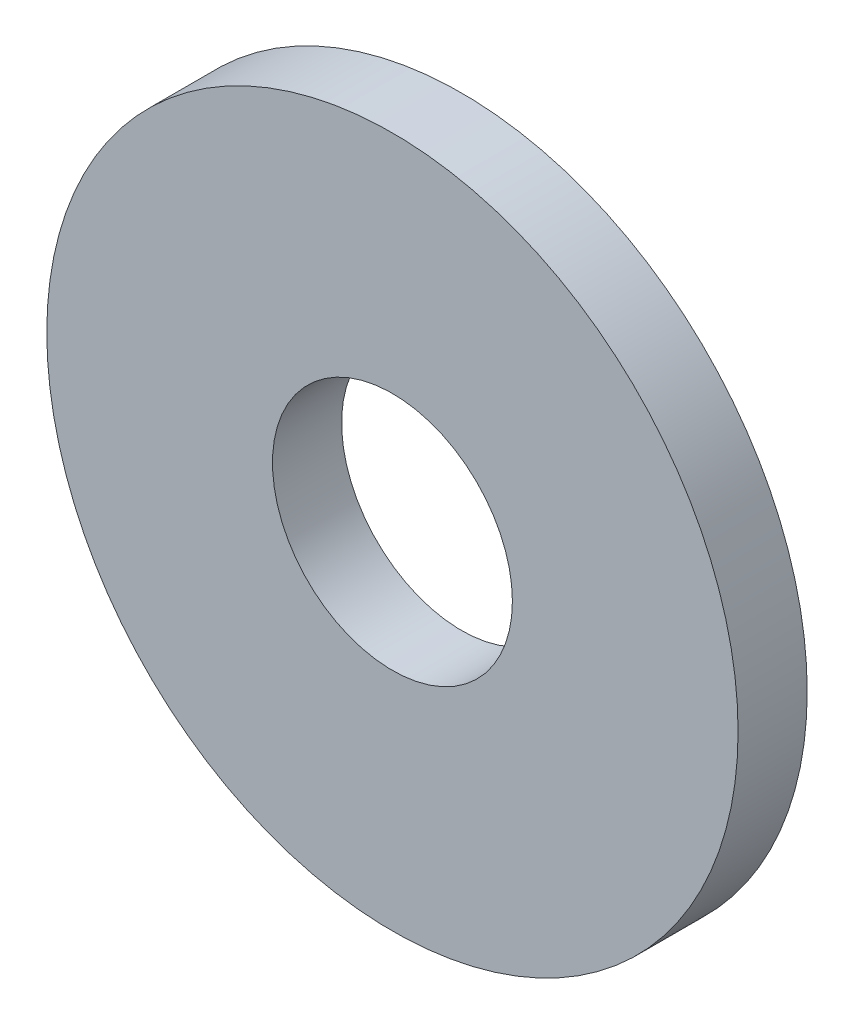
SolidWorks part; units mm, degrees
ref_plane "Front Plane" through (0, 0, 0) normal (0, 0, 1) x (1, 0, 0)
ref_plane "Top Plane" through (0, 0, 0) normal (0, 1, 0) x (1, 0, 0)
ref_plane "Right Plane" through (0, 0, 0) normal (1, 0, 0) x (0, 0, -1)
sketch "Sketch1" plane through (0, 0, 0) normal (0, 0, 1) x (1, 0, 0)
  circle A0 centre (0, 0) radius 8.5
  circle A1 centre (0, 0) radius 2.95
  dimension "D1" = 5.9
  dimension "D2" = 17
extrude "Boss-Extrude1" add sketch "Sketch1" along normal blind 1.7
equation "\"smallPulleyTeeth\"= 15"
equation "\"largePulleyTeeth\"= 30"
equation "\"eighthThick\"= 2.9mm"
equation "\"sixteenthThick\" = 1.7mm"
equation "\"wheelEighthThick\"=3.0mm"
equation "\"quarterThick\"=5.9mm"
equation "\"OD\" = 145mm"
equation "\"puckAngle\" = 60.5deg"
equation "\"puckDiam\" = 76.5mm"
equation "\"axlePress\" = 5.9mm"
equation "\"D1@Sketch1\"=\"axlePress\""
equation "\"D1@Boss-Extrude1\"=\"sixteenthThick\""
